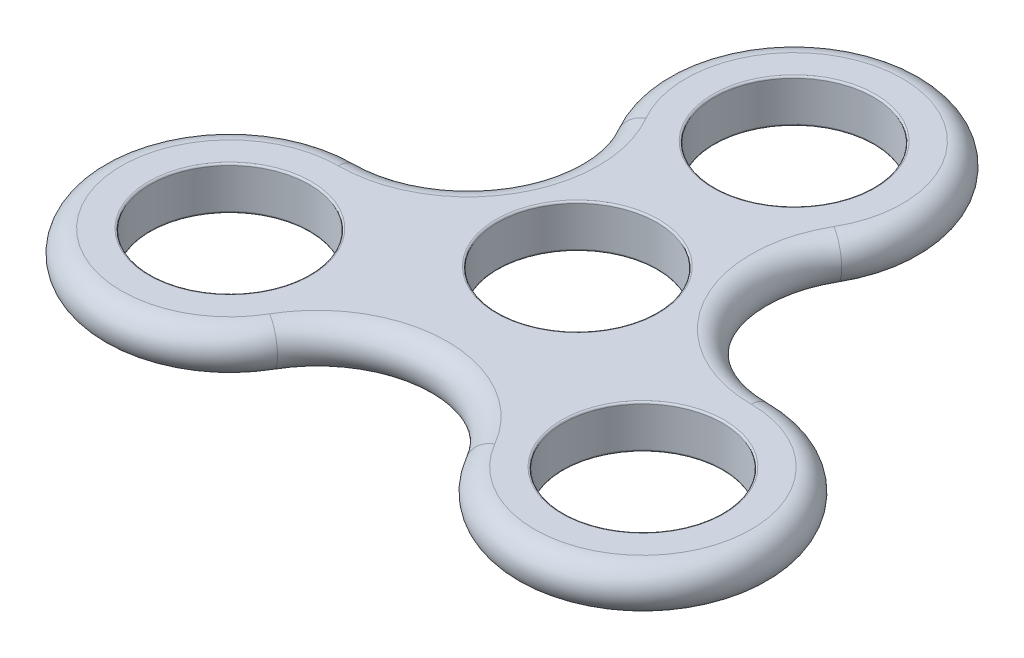
SolidWorks part; units mm, degrees
ref_plane "Front Plane" through (0, 0, 0) normal (0, 0, 1) x (1, 0, 0)
ref_plane "Top Plane" through (0, 0, 0) normal (0, 1, 0) x (1, 0, 0)
ref_plane "Right Plane" through (0, 0, 0) normal (1, 0, 0) x (0, 0, -1)
sketch "Sketch1" plane through (0, 0, 0) normal (0, 1, 0) x (1, 0, 0)
  circle A3 centre (0, 0) radius 11
  circle A4 centre (0, 30) radius 11
  circle A5 centre (28.5788, -19.5) radius 11
  circle A6 centre (-28.5788, -19.5) radius 11
  arc A7 (-28.5788, -1.5) -> (-12.9904, -28.5) centre (-28.5788, -19.5) ccw
  arc A8 (15.5885, 21) -> (-15.5885, 21) centre (0, 30) ccw
  arc A9 (12.9904, -28.5) -> (28.5788, -1.5) centre (28.5788, -19.5) ccw
  arc A10 (-15.5885, 21) -> (-28.5788, -1.5) centre (-28.5788, 13.5) cw
  arc A11 (15.5885, 21) -> (28.5788, -1.5) centre (28.5788, 13.5) ccw
  arc A12 (-12.9904, -28.5) -> (12.9904, -28.5) centre (0, -36) cw
  circle A14 centre (0, 30) radius 18 construction
  circle A15 centre (-28.5788, -19.5) radius 18 construction
  circle A16 centre (28.5788, -19.5) radius 18 construction
  point P2 (0, 0)
  point P6 (45.7923, -14.2373)
  point P13 (0, -3)
  point P14 (-11.3654, -14.2373)
  point P26 (0, 0)
  point P27 (18, 30)
  dimension "D1" = 3
  dimension "D2" = 22
  dimension "D5" = 15
  dimension "D3" = 30
  dimension "D4" = 7
extrude "Boss-Extrude2" add sketch "Sketch1" along normal blind 6
fillet "Fillet1" 2 edges at (0, 6, -48) (0, 0, -48) type full round first side face at (0, 6, 3) second side face at (28.5788, 0, 30.5) middle face at (0, 3, -34.5)
fillet "Fillet2" radius 0.25 8 edges at (-28.5788, 0, 30.5) (-28.5788, 6, 30.5) (28.5788, 0, 30.5) (28.5788, 6, 30.5) (0, 0, 11) (0, 6, 11) (0, 0, -19) (0, 6, -19)
